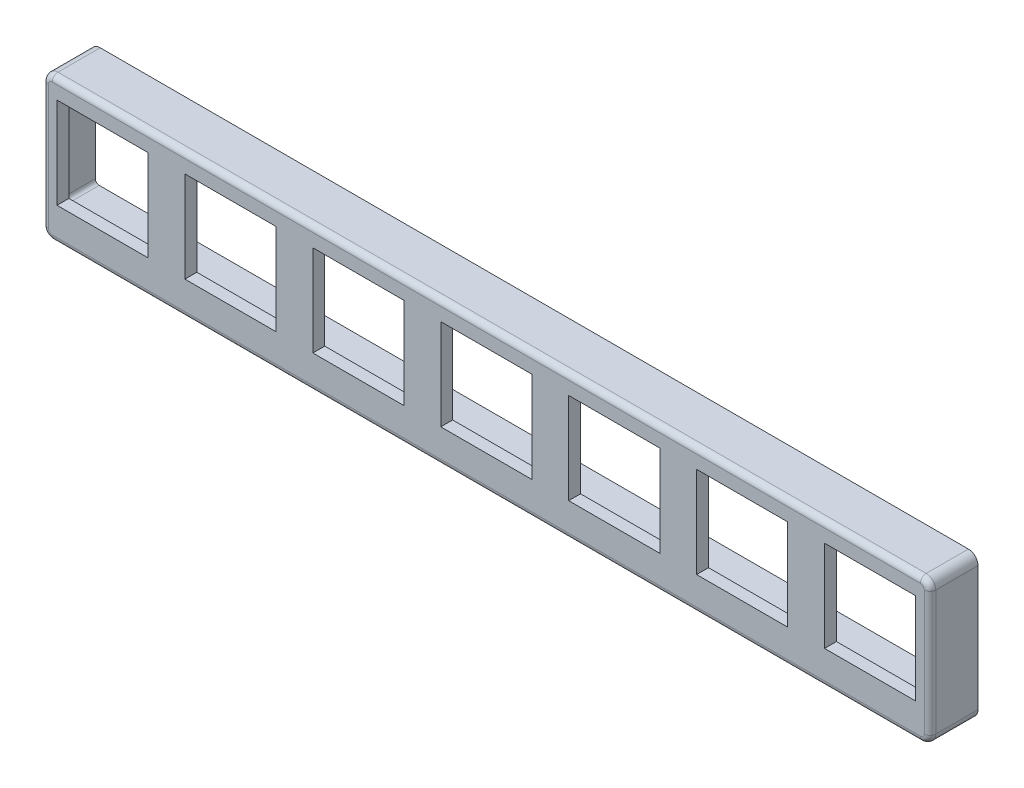
SolidWorks part; units mm, degrees
material "ABS PC"
ref_plane "Front Plane" through (0, 0, 0) normal (0, 0, 1) x (1, 0, 0)
ref_plane "Top Plane" through (0, 0, 0) normal (0, 1, 0) x (1, 0, 0)
ref_plane "Right Plane" through (0, 0, 0) normal (1, 0, 0) x (0, 0, -1)
sketch "Sketch1" plane through (0, 0, 0) normal (0, 0, 1) x (1, 0, 0)
  line L4 (-58.7375, -67.1355) -> (58.7375, -67.1355)
  line L5 (58.7375, -67.1355) -> (58.7375, -48.0855)
  line L6 (58.7375, -48.0855) -> (-58.7375, -48.0855)
  line L7 (-58.7375, -48.0855) -> (-58.7375, -67.1355)
  line L8 (-58.7375, -67.1355) -> (58.7375, -67.1355)
  line L9 (58.7375, -67.1355) -> (58.7375, -48.0855)
  line L10 (58.7375, -48.0855) -> (-58.7375, -48.0855)
  line L11 (-58.7375, -48.0855) -> (-58.7375, -67.1355)
  dimension "D1" = 0
extrude "Boss-Extrude1" add sketch "Sketch1" along normal up to surface (9.525 mm away)
sketch "Sketch2" plane through (0, 0, 0) normal (0, 0, 1) x (1, 0, 0)
  line L0 (35.56, -48.0855) -> (58.7375, -48.0855) construction
  line L1 (58.7375, -48.0855) -> (44.94, -39.2609) construction
  line L2 (38.1, -43.0055) -> (38.1, -45.5455) construction
  line L3 (-38.1, -45.5455) -> (-38.1, -43.0055) construction
  line L4 (-44.94, -39.2609) -> (-58.7375, -48.0855) construction
  line L5 (-58.7375, -48.0855) -> (-35.56, -48.0855) construction
  line L6 (35.56, -48.0855) -> (58.7375, -48.0855)
  line L7 (58.7375, -48.0855) -> (44.94, -39.2609)
  line L8 (38.1, -43.0055) -> (38.1, -45.5455)
  line L9 (-38.1, -45.5455) -> (-38.1, -43.0055)
  line L10 (-44.94, -39.2609) -> (-58.7375, -48.0855)
  line L11 (-58.7375, -48.0855) -> (-35.56, -48.0855)
  arc A0 (44.94, -39.2609) -> (38.1, -43.0055) centre (42.545, -43.0055) ccw construction
  arc A1 (35.56, -48.0855) -> (38.1, -45.5455) centre (35.56, -45.5455) ccw construction
  arc A2 (-38.1, -45.5455) -> (-35.56, -48.0855) centre (-35.56, -45.5455) ccw construction
  arc A3 (-38.1, -43.0055) -> (-44.94, -39.2609) centre (-42.545, -43.0055) ccw construction
  arc A4 (44.94, -39.2609) -> (38.1, -43.0055) centre (42.545, -43.0055) ccw
  arc A5 (35.56, -48.0855) -> (38.1, -45.5455) centre (35.56, -45.5455) ccw
  arc A6 (-38.1, -45.5455) -> (-35.56, -48.0855) centre (-35.56, -45.5455) ccw
  arc A7 (-38.1, -43.0055) -> (-44.94, -39.2609) centre (-42.545, -43.0055) ccw
extrude "Boss-Extrude2" add sketch "Sketch2" along normal up to surface (3.175 mm away)
hole_wizard "#6 Clearance Hole1" positions "Sketch4" profile "Sketch3" hole size "#6" standard "ANSI Inch" end condition through all
sketch "Sketch4" plane through (0, 0, 3.175) normal (0, 0, 1) x (1, 0, 0)
  point P0 (42.545, -43.0055)
  point P3 (-42.545, -43.0055)
sketch "Sketch3" plane through (42.545, -43.0055, 3.175) normal (1, 0, 0) x (0, -1, 0)
  line L0 (0, 0) -> (0, 3.175)
  line L1 (0, 3.175) -> (2.1526, 3.175)
  line L2 (2.1526, 3.175) -> (2.1526, 0)
  line L5 (2.1526, 0) -> (0, 0)
  line L11 (0, -6.35) -> (0, 107.95) construction
  dimension "Thru Hole Dia." = 4.3053
  dimension "Thru Hole Depth" = 3.175
sketch "Sketch5" plane through (0, 0, 9.525) normal (0, 0, 1) x (1, 0, 0)
  line L0 (56.8325, -50.5874) -> (44.7675, -50.5874) construction
  line L1 (44.7675, -50.5874) -> (44.7675, -62.6524) construction
  line L2 (44.7675, -62.6524) -> (56.8325, -62.6524) construction
  line L3 (56.8325, -62.6524) -> (56.8325, -50.5874) construction
  line L4 (39.8992, -62.6524) -> (39.8992, -50.5874) construction
  line L5 (39.8992, -50.5874) -> (27.8342, -50.5874) construction
  line L6 (27.8342, -50.5874) -> (27.8342, -62.6524) construction
  line L7 (27.8342, -62.6524) -> (39.8992, -62.6524) construction
  line L8 (10.9008, -50.5874) -> (10.9008, -62.6524) construction
  line L9 (10.9008, -62.6524) -> (22.9658, -62.6524) construction
  line L10 (22.9658, -62.6524) -> (22.9658, -50.5874) construction
  line L11 (22.9658, -50.5874) -> (10.9008, -50.5874) construction
  line L12 (6.0325, -50.5874) -> (-6.0325, -50.5874) construction
  line L13 (-6.0325, -50.5874) -> (-6.0325, -62.6524) construction
  line L14 (-6.0325, -62.6524) -> (6.0325, -62.6524) construction
  line L15 (6.0325, -62.6524) -> (6.0325, -50.5874) construction
  line L16 (-10.9008, -50.5874) -> (-22.9658, -50.5874) construction
  line L17 (-22.9658, -50.5874) -> (-22.9658, -62.6524) construction
  line L18 (-22.9658, -62.6524) -> (-10.9008, -62.6524) construction
  line L19 (-10.9008, -62.6524) -> (-10.9008, -50.5874) construction
  line L20 (-27.8342, -50.5874) -> (-39.8992, -50.5874) construction
  line L21 (-39.8992, -50.5874) -> (-39.8992, -62.6524) construction
  line L22 (-39.8992, -62.6524) -> (-27.8342, -62.6524) construction
  line L23 (-27.8342, -62.6524) -> (-27.8342, -50.5874) construction
  line L24 (-44.7675, -50.5874) -> (-56.8325, -50.5874) construction
  line L25 (-56.8325, -50.5874) -> (-56.8325, -62.6524) construction
  line L26 (-56.8325, -62.6524) -> (-44.7675, -62.6524) construction
  line L27 (-44.7675, -62.6524) -> (-44.7675, -50.5874) construction
  line L28 (56.8325, -50.5874) -> (44.7675, -50.5874)
  line L29 (44.7675, -50.5874) -> (44.7675, -62.6524)
  line L30 (44.7675, -62.6524) -> (56.8325, -62.6524)
  line L31 (56.8325, -62.6524) -> (56.8325, -50.5874)
  line L32 (39.8992, -62.6524) -> (39.8992, -50.5874)
  line L33 (39.8992, -50.5874) -> (27.8342, -50.5874)
  line L34 (27.8342, -50.5874) -> (27.8342, -62.6524)
  line L35 (27.8342, -62.6524) -> (39.8992, -62.6524)
  line L36 (10.9008, -50.5874) -> (10.9008, -62.6524)
  line L37 (10.9008, -62.6524) -> (22.9658, -62.6524)
  line L38 (22.9658, -62.6524) -> (22.9658, -50.5874)
  line L39 (22.9658, -50.5874) -> (10.9008, -50.5874)
  line L40 (6.0325, -50.5874) -> (-6.0325, -50.5874)
  line L41 (-6.0325, -50.5874) -> (-6.0325, -62.6524)
  line L42 (-6.0325, -62.6524) -> (6.0325, -62.6524)
  line L43 (6.0325, -62.6524) -> (6.0325, -50.5874)
  line L44 (-10.9008, -50.5874) -> (-22.9658, -50.5874)
  line L45 (-22.9658, -50.5874) -> (-22.9658, -62.6524)
  line L46 (-22.9658, -62.6524) -> (-10.9008, -62.6524)
  line L47 (-10.9008, -62.6524) -> (-10.9008, -50.5874)
  line L48 (-27.8342, -50.5874) -> (-39.8992, -50.5874)
  line L49 (-39.8992, -50.5874) -> (-39.8992, -62.6524)
  line L50 (-39.8992, -62.6524) -> (-27.8342, -62.6524)
  line L51 (-27.8342, -62.6524) -> (-27.8342, -50.5874)
  line L52 (-44.7675, -50.5874) -> (-56.8325, -50.5874)
  line L53 (-56.8325, -50.5874) -> (-56.8325, -62.6524)
  line L54 (-56.8325, -62.6524) -> (-44.7675, -62.6524)
  line L55 (-44.7675, -62.6524) -> (-44.7675, -50.5874)
extrude "Cut-Extrude1" cut sketch "Sketch5" against normal through all
sketch "Sketch7" plane through (0, 0, 0) normal (0, 0, -1) x (-1, 0, 0)
  line L56 (-56.8325, -62.6524) -> (-56.8325, -50.5874) construction
  line L57 (-58.1025, -49.3174) -> (58.1025, -49.3174)
  line L58 (-58.1025, -49.3174) -> (-58.1025, -63.9224)
  line L59 (-58.1025, -63.9224) -> (58.1025, -63.9224)
  line L60 (58.1025, -49.3174) -> (58.1025, -63.9224)
  line L61 (-58.1025, -49.3174) -> (58.1025, -63.9224) construction
  line L62 (-58.1025, -63.9224) -> (58.1025, -49.3174) construction
  line L63 (56.8325, -50.5874) -> (56.8325, -62.6524) construction
  line L64 (6.0325, -62.6524) -> (-6.0325, -62.6524) construction
  line L65 (-6.0325, -50.5874) -> (6.0325, -50.5874) construction
  point P4 (0, -56.6199)
  dimension "D1" = 1.27
  dimension "D2" = 1.27
  dimension "D3" = 1.27
  dimension "D4" = 1.27
extrude "Cut-Extrude2" cut sketch "Sketch7" against normal offset from surface (7.9502 mm away) 1.5748 up to face at (-50.8, -56.6199, 9.525)
sketch "Sketch8" plane through (0, 0, 0) normal (0, 0, -1) x (-1, 0, 0)
  line L0 (-58.7375, -67.1355) -> (-58.7375, -48.0855) construction
  line L1 (58.7375, -67.1355) -> (-58.7375, -67.1355)
  line L2 (58.7375, -67.1355) -> (58.7375, -38.5605)
  line L3 (58.7375, -38.5605) -> (-58.7375, -38.5605)
  line L4 (-58.7375, -67.1355) -> (-58.7375, -38.5605)
  line L5 (58.7375, -67.1355) -> (-58.7375, -38.5605) construction
  line L6 (58.7375, -38.5605) -> (-58.7375, -67.1355) construction
  arc A0 (-38.1, -43.0055) -> (-44.94, -39.2609) centre (-42.545, -43.0055) ccw construction
  point P4 (0, -52.848)
extrude "Cut-Extrude3" cut sketch "Sketch8" against normal up to surface (3.175 mm away) up to face at (-40.3924, -43.0055, 3.175)
fillet "Fillet2" radius 1.27 4 edges at (58.7375, -48.0855, 6.35) (-58.7375, -67.1355, 6.35) (-58.7375, -48.0855, 6.35) (58.7375, -67.1355, 6.35)
fillet "Fillet3" radius 0.762 8 edges at (-58.3655, -66.7635, 9.525) (-58.7375, -57.6105, 9.525) (-58.3655, -48.4575, 9.525) (0, -48.0855, 9.525) (58.3655, -48.4575, 9.525) (58.7375, -57.6105, 9.525) (58.3655, -66.7635, 9.525) (0, -67.1355, 9.525)
fillet "Fillet4" radius 0.508 8 edges at (-58.1025, -49.3174, 5.5626) (-58.1025, -63.9224, 5.5626) (58.1025, -63.9224, 5.5626) (58.1025, -49.3174, 5.5626) (-58.1025, -56.6199, 7.9502) (0, -63.9224, 7.9502) (58.1025, -56.6199, 7.9502) (0, -49.3174, 7.9502)
